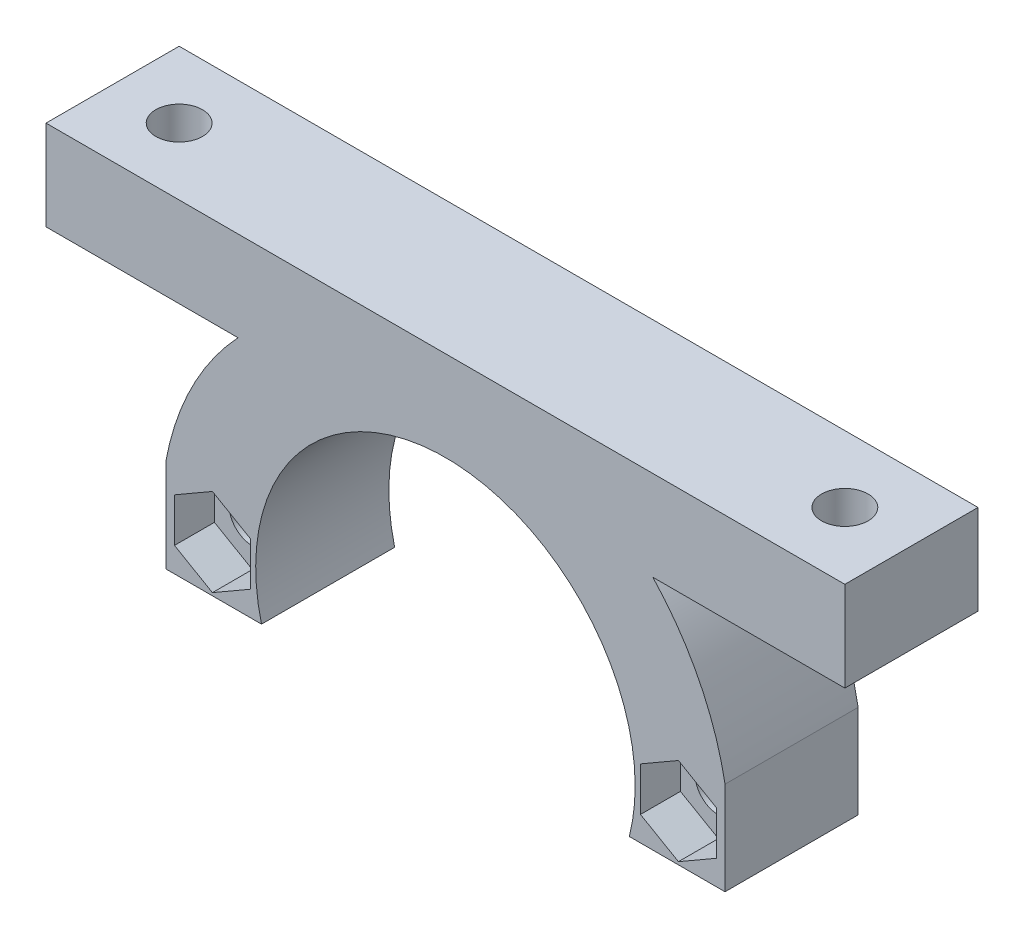
SolidWorks part; units mm, degrees
ref_plane "Plan de face" through (0, 0, 0) normal (0, 0, 1) x (1, 0, 0)
ref_plane "Plan de dessus" through (0, 0, 0) normal (0, 1, 0) x (1, 0, 0)
ref_plane "Plan de droite" through (0, 0, 0) normal (1, 0, 0) x (0, 0, -1)
sketch "Esquisse1" plane through (0, 0, 0) normal (0, 0, 1) x (1, 0, 0)
  line L0 (-21, 0) -> (21, 0) construction
  line L1 (-21, 3.5) -> (21, 3.5) construction
  line L2 (-21, 3.5) -> (-21, -3.5)
  line L3 (-21, -3.5) -> (21, -3.5) construction
  line L4 (21, 3.5) -> (21, -3.5)
  line L5 (-21, 3.5) -> (-13.8135, 3.5) construction
  line L6 (13.8135, 3.5) -> (21, 3.5) construction
  line L7 (-13.8135, 3.5) -> (-13.8135, -3.5) construction
  line L8 (-13.8135, -3.5) -> (-21, -3.5)
  line L9 (21, -3.5) -> (13.8135, -3.5)
  line L10 (13.8135, 3.5) -> (13.8135, -3.5) construction
  line L11 (0, 0) -> (0, 21) construction
  circle A0 centre (0, 0) radius 14.25 construction
  circle A1 centre (-17.5, 0) radius 1.75
  circle A2 centre (17.5, 0) radius 1.75
  arc A5 (-13.8135, -3.5) -> (13.8135, -3.5) centre (0, 0) cw
  arc A6 (-21, 3.5) -> (21, 3.5) centre (0, -0.35) cw
  point P13 (0, 0)
  point P21 (0, 21)
  dimension "D1" = 28.5
  dimension "D4" = 35
  dimension "D5" = 3.5
  dimension "D6" = 3.5
  dimension "D8" = 21
  dimension "D2" = 42
  dimension "D3" = 7
extrude "Boss.-Extru.1" add sketch "Esquisse1" along normal blind 10
sketch "Esquisse3" plane through (0, 0, 0) normal (0, 0, 1) x (1, 0, 0)
  line L0 (0, 21) -> (0, 14.25) construction
  line L2 (-30, 21) -> (30, 21)
  line L3 (-30, 21) -> (-30, 14.25)
  line L4 (-30, 14.25) -> (30, 14.25)
  line L5 (30, 21) -> (30, 14.25)
  arc A2 (21, 3.5) -> (-21, 3.5) centre (0, -0.35) ccw construction
  arc A3 (13.8135, -3.5) -> (-13.8135, -3.5) centre (0, 0) ccw construction
  point P6 (0, 21)
  point P12 (0, 21)
  dimension "D2" = 60
extrude "Boss.-Extru.2" add sketch "Esquisse3" along normal blind 10
sketch "Esquisse4" plane through (0, 21, 0) normal (0, 1, 0) x (1, 0, 0)
  line L0 (-30, -5) -> (30, -5) construction
  line L1 (-30, -10) -> (-30, 0) construction
  line L2 (30, -10) -> (30, 0) construction
  circle A0 centre (-25, -5) radius 1.75
  circle A1 centre (25, -5) radius 1.75
  dimension "D1" = 3.5
  dimension "D3" = 5
  dimension "D4" = 5
extrude "Enlèv. mat.-Extru.1" cut sketch "Esquisse4" against normal up to next
sketch "Esquisse5" plane through (0, 14.25, 0) normal (0, -1, 0) x (1, 0, 0)
  line L0 (25, 8.2909) -> (22.15, 6.6454)
  line L1 (22.15, 6.6454) -> (22.15, 3.3546)
  line L2 (22.15, 3.3546) -> (25, 1.7091)
  line L3 (25, 1.7091) -> (27.85, 3.3546)
  line L4 (27.85, 3.3546) -> (27.85, 6.6454)
  line L5 (27.85, 6.6454) -> (25, 8.2909)
  line L6 (25, 8.2909) -> (25, 1.7091) construction
  line L7 (22.15, 6.6454) -> (27.85, 6.6454) construction
  line L8 (-25, 8.2909) -> (-27.85, 6.6454)
  line L9 (-27.85, 6.6454) -> (-27.85, 3.3546)
  line L10 (-27.85, 3.3546) -> (-25, 1.7091)
  line L11 (-25, 1.7091) -> (-22.15, 3.3546)
  line L12 (-22.15, 3.3546) -> (-22.15, 6.6454)
  line L13 (-22.15, 6.6454) -> (-25, 8.2909)
  line L14 (-25, 8.2909) -> (-25, 1.7091) construction
  line L15 (-27.85, 6.6454) -> (-22.15, 6.6454) construction
  point P6 (-25, 5)
  point P14 (25, 5)
  point P15 (25, 5)
  point P18 (-25, 5)
  dimension "D1" = 120
  dimension "D2" = 5.7
  dimension "D3" = 120
  dimension "D4" = 5.7
extrude "Enlèv. mat.-Extru.2" cut sketch "Esquisse5" against normal blind 3
sketch "Esquisse6" plane through (0, 0, 10) normal (0, 0, 1) x (1, 0, 0)
  line L0 (-17.5, 3.2909) -> (-20.35, 1.6454)
  line L1 (-20.35, 1.6454) -> (-20.35, -1.6454)
  line L2 (-20.35, -1.6454) -> (-17.5, -3.2909)
  line L3 (-17.5, -3.2909) -> (-14.65, -1.6454)
  line L4 (-14.65, -1.6454) -> (-14.65, 1.6454)
  line L5 (-14.65, 1.6454) -> (-17.5, 3.2909)
  line L6 (-17.5, 3.2909) -> (-17.5, -3.2909) construction
  line L7 (-20.35, 1.6454) -> (-14.65, 1.6454) construction
  line L8 (17.5, 3.2909) -> (14.65, 1.6454)
  line L9 (14.65, 1.6454) -> (14.65, -1.6454)
  line L10 (14.65, -1.6454) -> (17.5, -3.2909)
  line L11 (17.5, -3.2909) -> (20.35, -1.6454)
  line L12 (20.35, -1.6454) -> (20.35, 1.6454)
  line L13 (20.35, 1.6454) -> (17.5, 3.2909)
  line L14 (17.5, 3.2909) -> (17.5, -3.2909) construction
  line L15 (14.65, 1.6454) -> (20.35, 1.6454) construction
  point P12 (-17.5, 0)
  point P13 (17.5, 0)
  point P15 (17.5, 0)
  point P18 (-17.5, 0)
  dimension "D1" = 120
  dimension "D2" = 5.7
  dimension "D3" = 120
  dimension "D4" = 5.7
extrude "Enlèv. mat.-Extru.3" cut sketch "Esquisse6" against normal blind 3
